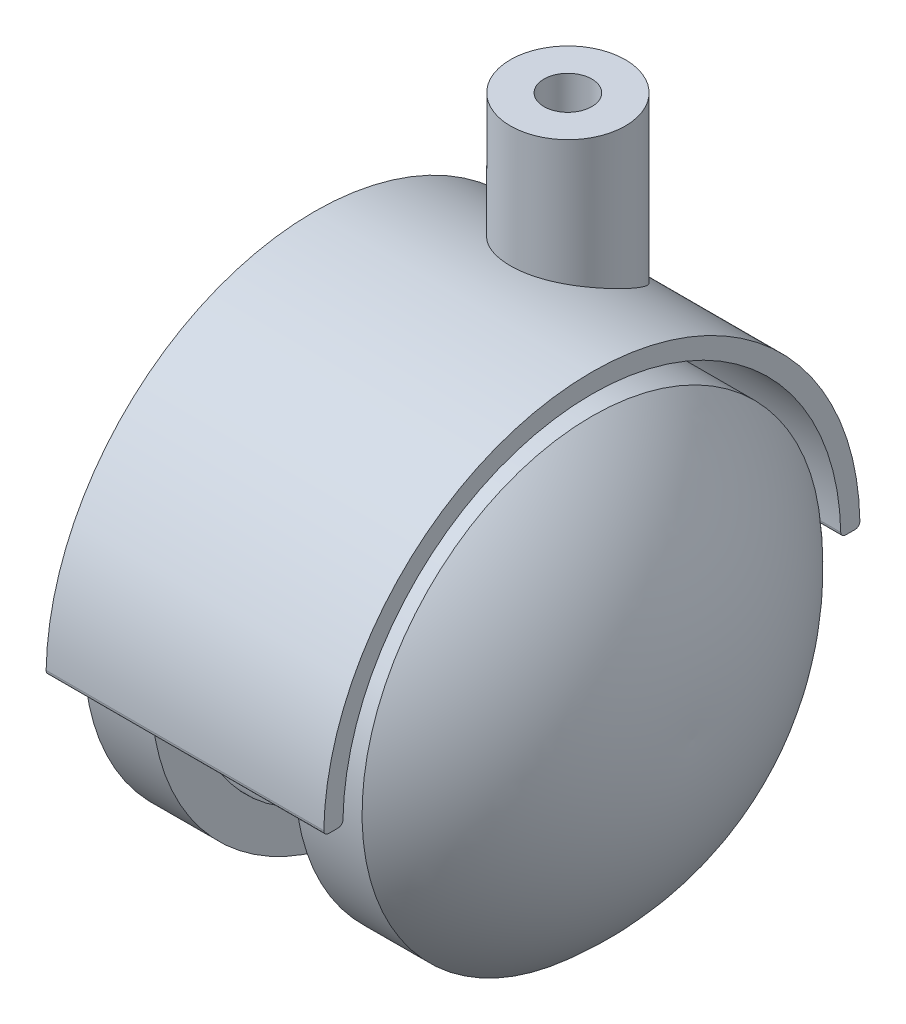
SolidWorks part; units mm, degrees
material "PF"
ref_plane "Front Plane" through (0, 0, 0) normal (0, 0, 1) x (1, 0, 0)
ref_plane "Top Plane" through (0, 0, 0) normal (0, 1, 0) x (1, 0, 0)
ref_plane "Right Plane" through (0, 0, 0) normal (1, 0, 0) x (0, 0, -1)
sketch "Sketch1" plane through (0, 0, 0) normal (1, 0, 0) x (0, 0, -1)
  circle A0 centre (0, 0) radius 24
  dimension "D1" = 48
extrude "Boss-Extrude1" add sketch "Sketch1" along normal blind 7
sketch "Sketch3" plane through (0, 0, 0) normal (0, 0, 1) x (1, 0, 0)
  line L0 (0, 0) -> (0, 24)
  line L1 (0, 0) -> (-10.5, 0)
  arc A0 (0, 24) -> (-10.5, 0) centre (19.4767, 1.1821) ccw
  dimension "D2" = 30
  dimension "D1" = 10.5
revolve "Revolve1" add sketch "Sketch3" angle 360 about L1
sketch "Sketch4" plane through (7, 0, 0) normal (1, 0, 0) x (0, 0, -1)
  circle A0 centre (0, 0) radius 7.5
  circle A1 centre (0, 0) radius 20
  dimension "D1" = 15
  dimension "D2" = 40
extrude "Cut-Extrude1" cut sketch "Sketch4" against normal blind 7
ref_plane "Plane1" through (14.5, 0, 0) normal (1, 0, 0) x (0, 0, -1)
sketch "Sketch5" plane through (7, 0, 0) normal (1, 0, 0) x (0, 0, -1)
  circle A0 centre (0, 0) radius 5
  dimension "D1" = 10
extrude "Boss-Extrude2" add sketch "Sketch5" along normal blind 7.5
mirror "Mirror8" about plane through (14.5, 0, 0) normal (1, 0, 0) of "Boss-Extrude2"
mirror "Mirror9" about plane through (14.5, 0, 0) normal (1, 0, 0) of "Boss-Extrude1"
mirror "Mirror10" about plane through (14.5, 0, 0) normal (1, 0, 0) of "Revolve1"
mirror "Mirror11" about plane through (14.5, 0, 0) normal (1, 0, 0) of "Cut-Extrude1"
sketch "Sketch6" plane through (0, 0, 0) normal (1, 0, 0) x (0, 0, -1)
  line L0 (-26.4953, 0) -> (-27.4955, 0)
  line L1 (26.4953, 0) -> (27.4955, 0)
  arc A0 (25.9954, 0.4906) -> (-25.9954, 0.4906) centre (0, 0) ccw
  arc A1 (27.9954, 0.5091) -> (-27.9954, 0.5091) centre (0, 0) ccw
  arc A2 (-27.4955, 0) -> (-27.9954, 0.5091) centre (-27.4955, 0.5) cw
  arc A3 (-26.4953, 0) -> (-25.9954, 0.4906) centre (-26.4953, 0.5) ccw
  arc A4 (26.4953, 0) -> (25.9954, 0.4906) centre (26.4953, 0.5) cw
  arc A5 (27.4955, 0) -> (27.9954, 0.5091) centre (27.4955, 0.5) ccw
  point P8 (-28, 0)
  point P11 (-26, 0)
  point P14 (26, 0)
  point P17 (28, 0)
  dimension "D1" = 26
  dimension "D2" = 28
  dimension "D3" = 0.5
extrude "Boss-Extrude3" add sketch "Sketch6" along normal blind 29 separate body
sketch "Sketch8" plane through (0, 0, 0) normal (0, 1, 0) x (1, 0, 0)
  line L0 (14.5, -38.185) -> (14.5, 38.185) construction
  circle A0 centre (14.5, 12) radius 6
  circle A1 centre (14.5, 12) radius 2.5
  dimension "D2" = 12
  dimension "D3" = 5
  dimension "D1" = 12
extrude "Boss-Extrude4" add sketch "Sketch8" along normal blind 40
sketch "Sketch9" plane through (0, 0, 0) normal (1, 0, 0) x (0, 0, -1)
  line L1 (-6.5, 6) -> (18.5, 6)
  line L2 (-6.5, 6) -> (-6.5, -12)
  line L3 (-6.5, -12) -> (18.5, -12)
  line L4 (18.5, 6) -> (18.5, -12)
  dimension "D1" = 18
  dimension "D2" = 25
  dimension "D3" = 18.5
  dimension "D4" = 6
extrude "Boss-Extrude5" add sketch "Sketch9" along normal blind 30
fillet "Fillet1" radius 10 2 edges at (15, 6, -18.5) (15, -12, -18.5)
fillet "Fillet2" radius 10 1 edges at (15, -12, 6.5)
